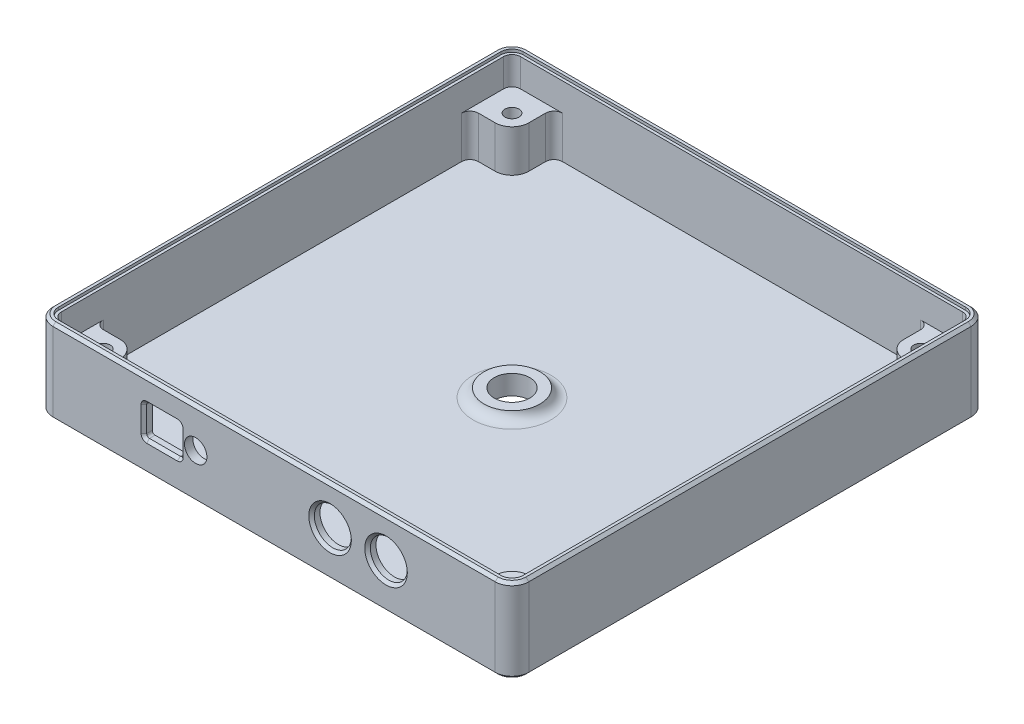
SolidWorks part; units mm, degrees
material "1060 Alloy"
ref_plane "Front Plane" through (0, 0, 0) normal (0, 0, 1) x (1, 0, 0)
ref_plane "Top Plane" through (0, 0, 0) normal (0, 1, 0) x (1, 0, 0)
ref_plane "Right Plane" through (0, 0, 0) normal (1, 0, 0) x (0, 0, -1)
sketch "Sketch1" plane through (0, 0, 0) normal (0, 1, 0) x (1, 0, 0)
  line L0 (42.5, 85) -> (42.5, 0) construction
  line L1 (0, 0) -> (85, 0)
  line L2 (0, 0) -> (0, 85)
  line L3 (0, 85) -> (85, 85)
  line L4 (85, 0) -> (85, 85)
  line L5 (1.5, 83.5) -> (83.5, 83.5) construction
  line L6 (1.5, 83.5) -> (1.5, 1.5) construction
  line L7 (1.5, 1.5) -> (83.5, 1.5) construction
  line L8 (83.5, 83.5) -> (83.5, 1.5) construction
  line L9 (0, 42.5) -> (85, 42.5) construction
  point P13 (83.5, 42.5)
  point P14 (42.5, 83.5)
  dimension "D1" = 82
  dimension "D2" = 1.5
  dimension "D3" = 1.5
extrude "Boss-Extrude1" add sketch "Sketch1" along normal blind 15
fillet "Fillet1" radius 3 4 edges at (0, 7.5, -85) (85, 7.5, -85) (85, 7.5, 0) (0, 7.5, 0)
chamfer "Chamfer1" distance 0.5 angle 45 8 edges at (0.8787, 0, -0.8787) (42.5, 0, 0) (84.1213, 0, -0.8787) (85, 0, -42.5) (84.1213, 0, -84.1213) (42.5, 0, -85) (0.8787, 0, -84.1213) (0, 0, -42.5)
chamfer "Chamfer2" distance 0.5 angle 45 8 edges at (84.1213, 15, -84.1213) (85, 15, -42.5) (84.1213, 15, -0.8787) (42.5, 15, 0) (0.8787, 15, -0.8787) (0, 15, -42.5) (0.8787, 15, -84.1213) (42.5, 15, -85)
sketch "Sketch2" plane through (0, 15, 0) normal (0, 1, 0) x (1, 0, 0)
  line L12 (83.5, 3) -> (83.5, 82)
  line L13 (82, 83.5) -> (3, 83.5)
  line L14 (1.5, 82) -> (1.5, 3)
  line L15 (3, 1.5) -> (82, 1.5)
  line L16 (83.5, 3) -> (83.5, 82)
  line L17 (82, 83.5) -> (3, 83.5)
  line L18 (1.5, 82) -> (1.5, 3)
  line L19 (3, 1.5) -> (82, 1.5)
  arc A8 (83.5, 82) -> (82, 83.5) centre (82, 82) ccw
  arc A9 (3, 83.5) -> (1.5, 82) centre (3, 82) ccw
  arc A10 (1.5, 3) -> (3, 1.5) centre (3, 3) ccw
  arc A11 (82, 1.5) -> (83.5, 3) centre (82, 3) ccw
  arc A12 (83.5, 82) -> (82, 83.5) centre (82, 82) ccw
  arc A13 (3, 83.5) -> (1.5, 82) centre (3, 82) ccw
  arc A14 (1.5, 3) -> (3, 1.5) centre (3, 3) ccw
  arc A15 (82, 1.5) -> (83.5, 3) centre (82, 3) ccw
  dimension "D1" = 1
extrude "Cut-Extrude1" cut sketch "Sketch2" against normal offset from surface (11.5 mm away) 3.5 up to face at (42.5, 0, -42.5)
sketch "Sketch3" plane through (0, 0, 0) normal (0, -1, 0) x (1, 0, 0)
  line L0 (0.5, -42.5) -> (84.5, -42.5) construction
  line L1 (0.5, -3) -> (0.5, -82) construction
  line L2 (84.5, -82) -> (84.5, -3) construction
  line L3 (42.5, -0.5) -> (42.5, -84.5) construction
  line L4 (82, -0.5) -> (3, -0.5) construction
  line L5 (3, -84.5) -> (82, -84.5) construction
  point P12 (42.5, -42.5)
hole_wizard "1/4 (0.25) Diameter Hole1" positions "3DSketch2" profile "Sketch5" hole size "1/4" standard "ANSI Inch" end condition through all
sketch3d "3DSketch2"
  point P0 (42.5, 0, -42.5)
sketch "Sketch5" plane through (42.5, 0, -42.5) normal (1, 0, 0) x (0, 0, -1)
  line L0 (0, 0) -> (0, 15)
  line L1 (0, 15) -> (3.175, 15)
  line L2 (3.175, 15) -> (3.175, 0)
  line L5 (3.175, 0) -> (0, 0)
  line L11 (0, -6.35) -> (0, 107.95) construction
  dimension "Thru Hole Dia." = 6.35
  dimension "Thru Hole Depth" = 15
sketch "Sketch6" plane through (0, 3.5, 0) normal (0, 1, 0) x (1, 0, 0)
  line L0 (6, 1.5) -> (6, 83.5) construction
  line L1 (3, 1.5) -> (82, 1.5) construction
  line L2 (82, 83.5) -> (3, 83.5) construction
  line L3 (79, 84.5) -> (79, 1.5) construction
  line L4 (82, 84.5) -> (3, 84.5) construction
  line L5 (3, 1.5) -> (82, 1.5) construction
  line L6 (84.5, 6) -> (1.5, 6) construction
  line L7 (84.5, 3) -> (84.5, 82) construction
  line L8 (1.5, 82) -> (1.5, 3) construction
  line L9 (1.5, 79) -> (83.5, 79) construction
  line L10 (83.5, 3) -> (83.5, 82) construction
  line L11 (42.5, 79) -> (42.5, 85) construction
  line L12 (3, 85) -> (82, 85) construction
  line L13 (79, 43) -> (85, 43) construction
  line L14 (85, 82) -> (85, 3) construction
  line L15 (9, 79) -> (9, 83.5)
  line L16 (1.5, 82) -> (1.5, 3) construction
  line L17 (6, 42.5) -> (0, 42.5) construction
  line L18 (0, 3) -> (0, 82) construction
  line L19 (43, 6) -> (43, 0) construction
  line L20 (82, 0) -> (3, 0) construction
  line L21 (82, 83.5) -> (3, 83.5) construction
  line L22 (6, 76) -> (1.5, 76)
  line L23 (79, 76) -> (83.5, 76)
  line L24 (76, 79) -> (76, 83.5)
  line L25 (9, 6) -> (9, 1.5)
  line L26 (6, 9) -> (1.5, 9)
  line L27 (76, 6) -> (76, 1.5)
  line L28 (79, 9) -> (83.5, 9)
  line L29 (83.5, 3) -> (83.5, 82) construction
  line L30 (82, 83.5) -> (3, 83.5)
  line L31 (1.5, 82) -> (1.5, 3)
  line L32 (3, 1.5) -> (82, 1.5)
  line L33 (83.5, 3) -> (83.5, 82)
  circle A0 centre (6, 79) radius 3
  circle A1 centre (79, 79) radius 3
  circle A2 centre (79, 6) radius 3
  circle A3 centre (6, 6) radius 3
  arc A4 (3, 83.5) -> (1.5, 82) centre (3, 82) ccw construction
  arc A5 (1.5, 3) -> (3, 1.5) centre (3, 3) ccw construction
  arc A6 (82, 1.5) -> (83.5, 3) centre (82, 3) ccw construction
  arc A7 (83.5, 82) -> (82, 83.5) centre (82, 82) ccw construction
  arc A8 (3, 83.5) -> (1.5, 82) centre (3, 82) ccw
  arc A9 (1.5, 3) -> (3, 1.5) centre (3, 3) ccw
  arc A10 (82, 1.5) -> (83.5, 3) centre (82, 3) ccw
  arc A11 (83.5, 82) -> (82, 83.5) centre (82, 82) ccw
  arc M10 (82, 1.5) -> (83.5, 3) centre (82, 3) ccw
  line M11 (83.5, 3) -> (83.5, 82)
  arc M12 (83.5, 82) -> (82, 83.5) centre (82, 82) ccw
  line M13 (82, 83.5) -> (3, 83.5)
  arc M14 (3, 83.5) -> (1.5, 82) centre (3, 82) ccw
  line M15 (1.5, 82) -> (1.5, 3)
  arc M16 (1.5, 3) -> (3, 1.5) centre (3, 3) ccw
  line M17 (3, 1.5) -> (82, 1.5)
  dimension "D3" = 6
  dimension "D1" = 73
  dimension "D2" = 73
extrude "Boss-Extrude2" add sketch "Sketch6" along normal blind 6 contours A3 | A3 L26 L25 M15 M16 M17 | A0 L15 L22 M13 M14 M15 | A0 | A1 L23 L24 M11 M12 M13 | A2 | A2 L27 L28 M17 M10 M11
fillet "Fillet2" radius 1.5 8 edges at (9, 6.5, -83.5) (76, 6.5, -83.5) (83.5, 6.5, -76) (83.5, 6.5, -9) (76, 6.5, -1.5) (9, 6.5, -1.5) (1.5, 6.5, -9) (1.5, 6.5, -76)
sketch "Sketch7" plane through (0, 3.5, 0) normal (0, 1, 0) x (1, 0, 0)
  line L12 (74.5, 83.5) -> (10.5, 83.5)
  line L13 (9, 82) -> (9, 79)
  line L14 (6, 76) -> (3, 76)
  line L15 (1.5, 74.5) -> (1.5, 10.5)
  line L16 (3, 9) -> (6, 9)
  line L17 (9, 6) -> (9, 3)
  line L18 (10.5, 1.5) -> (74.5, 1.5)
  line L19 (76, 3) -> (76, 6)
  line L20 (79, 9) -> (82, 9)
  line L21 (83.5, 10.5) -> (83.5, 74.5)
  line L22 (82, 76) -> (79, 76)
  line L23 (76, 79) -> (76, 82)
  line L24 (74.5, 83.5) -> (10.5, 83.5)
  line L25 (9, 82) -> (9, 79)
  line L26 (6, 76) -> (3, 76)
  line L27 (1.5, 74.5) -> (1.5, 10.5)
  line L28 (3, 9) -> (6, 9)
  line L29 (9, 6) -> (9, 3)
  line L30 (10.5, 1.5) -> (74.5, 1.5)
  line L31 (76, 3) -> (76, 6)
  line L32 (79, 9) -> (82, 9)
  line L33 (83.5, 10.5) -> (83.5, 74.5)
  line L34 (82, 76) -> (79, 76)
  line L35 (76, 79) -> (76, 82)
  circle A0 centre (42.5, 42.5) radius 5
  arc A12 (10.5, 83.5) -> (9, 82) centre (10.5, 82) ccw
  arc A13 (6, 76) -> (9, 79) centre (6, 79) ccw
  arc A14 (3, 76) -> (1.5, 74.5) centre (3, 74.5) ccw
  arc A15 (1.5, 10.5) -> (3, 9) centre (3, 10.5) ccw
  arc A16 (9, 6) -> (6, 9) centre (6, 6) ccw
  arc A17 (9, 3) -> (10.5, 1.5) centre (10.5, 3) ccw
  arc A18 (74.5, 1.5) -> (76, 3) centre (74.5, 3) ccw
  arc A19 (79, 9) -> (76, 6) centre (79, 6) ccw
  arc A20 (82, 9) -> (83.5, 10.5) centre (82, 10.5) ccw
  arc A21 (83.5, 74.5) -> (82, 76) centre (82, 74.5) ccw
  arc A22 (76, 79) -> (79, 76) centre (79, 79) ccw
  arc A23 (76, 82) -> (74.5, 83.5) centre (74.5, 82) ccw
  arc A24 (10.5, 83.5) -> (9, 82) centre (10.5, 82) ccw
  arc A25 (6, 76) -> (9, 79) centre (6, 79) ccw
  arc A26 (3, 76) -> (1.5, 74.5) centre (3, 74.5) ccw
  arc A27 (1.5, 10.5) -> (3, 9) centre (3, 10.5) ccw
  arc A28 (9, 6) -> (6, 9) centre (6, 6) ccw
  arc A29 (9, 3) -> (10.5, 1.5) centre (10.5, 3) ccw
  arc A30 (74.5, 1.5) -> (76, 3) centre (74.5, 3) ccw
  arc A31 (79, 9) -> (76, 6) centre (79, 6) ccw
  arc A32 (82, 9) -> (83.5, 10.5) centre (82, 10.5) ccw
  arc A33 (83.5, 74.5) -> (82, 76) centre (82, 74.5) ccw
  arc A34 (76, 79) -> (79, 76) centre (79, 79) ccw
  arc A35 (76, 82) -> (74.5, 83.5) centre (74.5, 82) ccw
  dimension "D2" = 10
  dimension "D1" = 0
extrude "Cut-Extrude2" cut sketch "Sketch7" against normal blind 1.5
sketch "Sketch8" plane through (0, 0, -85) normal (0, 0, -1) x (-1, 0, 0)
  line L0 (0, 14.5) -> (0, 0.5) construction
  line L1 (-42, 4.5) -> (-18, 4.5)
  line L2 (-42, 4.5) -> (-42, 10.5)
  line L3 (-42, 10.5) -> (-18, 10.5)
  line L4 (-18, 4.5) -> (-18, 10.5)
  line L5 (-42, 4.5) -> (-18, 10.5) construction
  line L6 (-42, 10.5) -> (-18, 4.5) construction
  line L7 (-45.5587, 0.5) -> (-45.5587, 14.5) construction
  line L8 (-82, 0.5) -> (-3, 0.5) construction
  line L9 (-3, 14.5) -> (-82, 14.5) construction
  line L10 (-45.5587, 2) -> (-15.1888, 2) construction
  line L11 (-3, 0) -> (-82, 0) construction
  line L12 (-42, 7.5) -> (-18, 7.5) construction
  point P0 (-30, 7.5)
  point P19 (-45.5587, 7.5)
  dimension "D1" = 6
  dimension "D2" = 24
  dimension "D3" = 18
  dimension "D4" = 2.5
  dimension "D5" = 2
extrude "Cut-Extrude3" [suppressed] cut sketch "Sketch8" against normal up to next
fillet "Fillet3" [suppressed] radius 1
chamfer "Chamfer3" [suppressed] distance 1 angle 45
fillet "Fillet4" radius 2 1 edges at (42.5, 2, -37.5)
ref_plane "Plane1" through (10.5, 9.5, -1.5) normal (0, 1, 0) x (1, 0, 0)
sketch "Sketch11" plane through (0, 0, 0) normal (0, 0, 1) x (1, 0, 0)
  line L4 (25.5, 5.5538) -> (25.5, 10.5538)
  line L5 (25.5, 10.5538) -> (19.5, 10.5538)
  line L6 (19.5, 10.5538) -> (19.5, 5.5538)
  line L7 (19.5, 5.5538) -> (25.5, 5.5538)
  line L8 (25.5, 5.5538) -> (25.5, 10.5538)
  line L9 (25.5, 10.5538) -> (19.5, 10.5538)
  line L10 (19.5, 10.5538) -> (19.5, 5.5538)
  line L11 (19.5, 5.5538) -> (25.5, 5.5538)
  line L12 (25.25, 10.8038) -> (19.75, 10.8038)
  line L13 (25.75, 5.8038) -> (25.75, 10.3038)
  line L14 (19.75, 5.3038) -> (25.25, 5.3038)
  line L15 (19.25, 10.3038) -> (19.25, 5.8038)
  line L16 (25.25, 10.8038) -> (19.75, 10.8038)
  line L17 (25.75, 5.8038) -> (25.75, 10.3038)
  line L18 (19.75, 5.3038) -> (25.25, 5.3038)
  line L19 (19.25, 10.3038) -> (19.25, 5.8038)
  circle A1 centre (62.502, 8.0538) radius 2.8
  circle A2 centre (62.502, 8.0538) radius 2.8
  circle A3 centre (52.502, 8.0538) radius 2.8
  circle A4 centre (52.502, 8.0538) radius 2.8
  circle A5 centre (28.5001, 8.0568) radius 2
  circle A6 centre (28.5001, 8.0568) radius 2
  arc A10 (25.75, 10.3038) -> (25.25, 10.8038) centre (25.25, 10.3038) ccw
  arc A11 (25.25, 5.3038) -> (25.75, 5.8038) centre (25.25, 5.8038) ccw
  arc A12 (19.25, 5.8038) -> (19.75, 5.3038) centre (19.75, 5.8038) ccw
  arc A13 (19.75, 10.8038) -> (19.25, 10.3038) centre (19.75, 10.3038) ccw
  arc A14 (25.75, 10.3038) -> (25.25, 10.8038) centre (25.25, 10.3038) ccw
  arc A15 (25.25, 5.3038) -> (25.75, 5.8038) centre (25.25, 5.8038) ccw
  arc A16 (19.25, 5.8038) -> (19.75, 5.3038) centre (19.75, 5.8038) ccw
  arc A17 (19.75, 10.8038) -> (19.25, 10.3038) centre (19.75, 10.3038) ccw
  spline S1 degree 3 poles (65.785, 7.6262) (65.8105, 8.0538) (65.785, 8.4815) (65.6537, 9.1347) (65.2425, 10.0473) (64.1463, 11.0616) (62.502, 11.5) (60.8577, 11.0616) (59.7616, 10.0473) (59.3504, 9.1347) (59.2191, 8.4815) (59.1935, 8.0538) (59.2191, 7.6262) (59.3504, 6.9729) (59.7616, 6.0604) (60.8577, 5.0461) (62.502, 4.6077) (64.1463, 5.0461) (65.2425, 6.0604) (65.6537, 6.9729) (65.785, 7.6262) (65.8105, 8.0538) (65.785, 8.4815) knots -0.125 -0.0625 -0.03125 0 0.03125 0.0625 0.125 0.1875 0.25 0.3125 0.375 0.4375 0.46875 0.5 0.53125 0.5625 0.625 0.6875 0.75 0.8125 0.875 0.9375 0.96875 1 1.03125 1.0625 1.125 only from (65.802, 8.0538) to (65.802, 8.0538)
  spline S2 degree 3 poles (65.785, 7.6262) (65.8105, 8.0538) (65.785, 8.4815) (65.6537, 9.1347) (65.2425, 10.0473) (64.1463, 11.0616) (62.502, 11.5) (60.8577, 11.0616) (59.7616, 10.0473) (59.3504, 9.1347) (59.2191, 8.4815) (59.1935, 8.0538) (59.2191, 7.6262) (59.3504, 6.9729) (59.7616, 6.0604) (60.8577, 5.0461) (62.502, 4.6077) (64.1463, 5.0461) (65.2425, 6.0604) (65.6537, 6.9729) (65.785, 7.6262) (65.8105, 8.0538) (65.785, 8.4815) knots -0.125 -0.0625 -0.03125 0 0.03125 0.0625 0.125 0.1875 0.25 0.3125 0.375 0.4375 0.46875 0.5 0.53125 0.5625 0.625 0.6875 0.75 0.8125 0.875 0.9375 0.96875 1 1.03125 1.0625 1.125 only from (65.802, 8.0538) to (65.802, 8.0538)
  spline S3 degree 3 poles (55.785, 7.6262) (55.8105, 8.0538) (55.785, 8.4815) (55.6537, 9.1347) (55.2425, 10.0473) (54.1463, 11.0616) (52.502, 11.5) (50.8577, 11.0616) (49.7616, 10.0473) (49.3504, 9.1347) (49.2191, 8.4815) (49.1935, 8.0538) (49.2191, 7.6262) (49.3504, 6.9729) (49.7616, 6.0604) (50.8577, 5.0461) (52.502, 4.6077) (54.1463, 5.0461) (55.2425, 6.0604) (55.6537, 6.9729) (55.785, 7.6262) (55.8105, 8.0538) (55.785, 8.4815) knots -0.125 -0.0625 -0.03125 0 0.03125 0.0625 0.125 0.1875 0.25 0.3125 0.375 0.4375 0.46875 0.5 0.53125 0.5625 0.625 0.6875 0.75 0.8125 0.875 0.9375 0.96875 1 1.03125 1.0625 1.125 only from (55.802, 8.0538) to (55.802, 8.0538)
  spline S4 degree 3 poles (55.785, 7.6262) (55.8105, 8.0538) (55.785, 8.4815) (55.6537, 9.1347) (55.2425, 10.0473) (54.1463, 11.0616) (52.502, 11.5) (50.8577, 11.0616) (49.7616, 10.0473) (49.3504, 9.1347) (49.2191, 8.4815) (49.1935, 8.0538) (49.2191, 7.6262) (49.3504, 6.9729) (49.7616, 6.0604) (50.8577, 5.0461) (52.502, 4.6077) (54.1463, 5.0461) (55.2425, 6.0604) (55.6537, 6.9729) (55.785, 7.6262) (55.8105, 8.0538) (55.785, 8.4815) knots -0.125 -0.0625 -0.03125 0 0.03125 0.0625 0.125 0.1875 0.25 0.3125 0.375 0.4375 0.46875 0.5 0.53125 0.5625 0.625 0.6875 0.75 0.8125 0.875 0.9375 0.96875 1 1.03125 1.0625 1.125 only from (55.802, 8.0538) to (55.802, 8.0538)
  dimension "D1" = 0
  dimension "D2" = 0
  dimension "D3" = 0
  dimension "D4" = 0
  dimension "D5" = 0
  dimension "D6" = 0
  dimension "D7" = 0
extrude "Cut-Extrude4" cut sketch "Sketch11" against normal blind 10 contours L16 A17 L19 A16 L18 A15 L17 A14 L11 L10 L9 L8 | L10 L11 L8 L9 | A6 | S4 A4 | A4 | A2 | S2 A2
chamfer "Chamfer4" distance 0.5 angle 45 10 edges at (25.75, 8.0538, 0) (25.6035, 10.6574, 0) (22.5, 10.8038, 0) (19.3964, 10.6574, 0) (25.6035, 5.4503, 0) (19.25, 8.0538, 0) (19.3964, 5.4503, 0) (22.5, 5.3038, 0)
sketch "Sketch12" plane through (0, 15, 0) normal (0, 1, 0) x (1, 0, 0)
  line L0 (82, 83.5) -> (3, 83.5) construction
  line L1 (1.5, 82) -> (1.5, 3) construction
  line L2 (83.5, 3) -> (83.5, 82) construction
  line L3 (3, 1.5) -> (82, 1.5) construction
  line L4 (82, 83.5) -> (3, 83.5)
  line L5 (1.5, 82) -> (1.5, 3)
  line L6 (83.5, 3) -> (83.5, 82)
  line L7 (3, 1.5) -> (82, 1.5)
  line L8 (3, 1) -> (82, 1)
  line L9 (84, 3) -> (84, 82)
  line L10 (82, 84) -> (3, 84)
  line L11 (1, 82) -> (1, 3)
  arc A0 (3, 83.5) -> (1.5, 82) centre (3, 82) ccw construction
  arc A1 (83.5, 82) -> (82, 83.5) centre (82, 82) ccw construction
  arc A2 (82, 1.5) -> (83.5, 3) centre (82, 3) ccw construction
  arc A3 (1.5, 3) -> (3, 1.5) centre (3, 3) ccw construction
  arc A4 (3, 83.5) -> (1.5, 82) centre (3, 82) ccw
  arc A5 (83.5, 82) -> (82, 83.5) centre (82, 82) ccw
  arc A6 (82, 1.5) -> (83.5, 3) centre (82, 3) ccw
  arc A7 (1.5, 3) -> (3, 1.5) centre (3, 3) ccw
  arc A8 (1, 3) -> (3, 1) centre (3, 3) ccw
  arc A9 (82, 1) -> (84, 3) centre (82, 3) ccw
  arc A10 (84, 82) -> (82, 84) centre (82, 82) ccw
  arc A11 (3, 84) -> (1, 82) centre (3, 82) ccw
  dimension "D1" = 0.5
extrude "Cut-Extrude5" cut sketch "Sketch12" against normal blind 0.5
sketch "Sketch13" plane through (0, 9.5, 0) normal (0, 1, 0) x (1, 0, 0)
  circle A0 centre (6, 79) radius 1.25
  circle A1 centre (79, 79) radius 1.25
  circle A2 centre (79, 6) radius 1.25
  circle A3 centre (6, 6) radius 1.25
  dimension "D1" = 2.5
extrude "Cut-Extrude6" cut sketch "Sketch13" against normal blind 7
